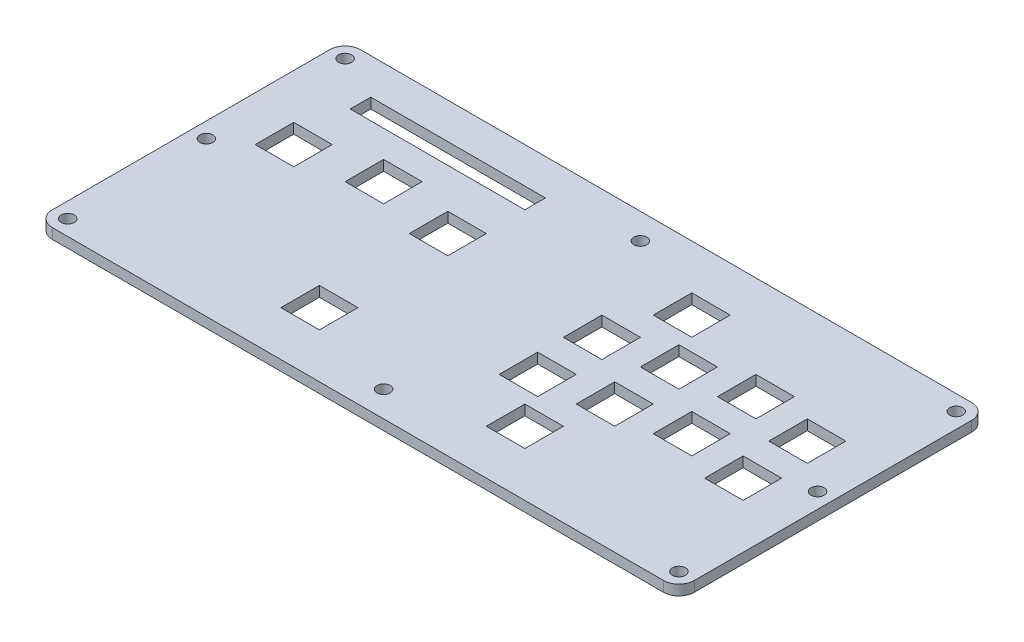
SolidWorks part; units mm, degrees
ref_plane "前视基准面" through (0, 0, 0) normal (0, 0, 1) x (1, 0, 0)
ref_plane "上视基准面" through (0, 0, 0) normal (0, 1, 0) x (1, 0, 0)
ref_plane "右视基准面" through (0, 0, 0) normal (1, 0, 0) x (0, 0, -1)
sketch "草图1" plane through (0, 0, 0) normal (0, 1, 0) x (1, 0, 0)
  line L0 (26.7276, 134.0406) -> (264.7276, 134.0406)
  line L1 (270.7276, 128.0406) -> (270.7276, 20.0406)
  line L2 (264.7276, 14.0406) -> (26.7276, 14.0406)
  line L3 (20.7276, 20.0406) -> (20.7276, 128.0406)
  line L4 (38.2276, 96.5406) -> (53.2276, 96.5406)
  line L5 (53.2276, 96.5406) -> (53.2276, 81.5406)
  line L6 (53.2276, 81.5406) -> (38.2276, 81.5406)
  line L7 (38.2276, 81.5406) -> (38.2276, 96.5406)
  line L8 (68.2276, 101.5406) -> (83.2276, 101.5406)
  line L9 (83.2276, 101.5406) -> (83.2276, 86.5406)
  line L10 (83.2276, 86.5406) -> (68.2276, 86.5406)
  line L11 (68.2276, 86.5406) -> (68.2276, 101.5406)
  line L12 (163.2276, 91.5406) -> (178.2276, 91.5406)
  line L13 (178.2276, 91.5406) -> (178.2276, 76.5406)
  line L14 (178.2276, 76.5406) -> (163.2276, 76.5406)
  line L15 (163.2276, 76.5406) -> (163.2276, 91.5406)
  line L16 (98.2276, 46.5406) -> (113.2276, 46.5406)
  line L17 (113.2276, 46.5406) -> (113.2276, 31.5406)
  line L18 (113.2276, 31.5406) -> (98.2276, 31.5406)
  line L19 (98.2276, 31.5406) -> (98.2276, 46.5406)
  line L20 (98.2276, 96.5406) -> (113.2276, 96.5406)
  line L21 (113.2276, 96.5406) -> (113.2276, 81.5406)
  line L22 (113.2276, 81.5406) -> (98.2276, 81.5406)
  line L23 (98.2276, 81.5406) -> (98.2276, 96.5406)
  line L24 (173.2276, 116.5406) -> (188.2276, 116.5406)
  line L25 (188.2276, 116.5406) -> (188.2276, 101.5406)
  line L26 (188.2276, 101.5406) -> (173.2276, 101.5406)
  line L27 (173.2276, 101.5406) -> (173.2276, 116.5406)
  line L28 (188.2276, 96.5406) -> (203.2276, 96.5406)
  line L29 (203.2276, 96.5406) -> (203.2276, 81.5406)
  line L30 (203.2276, 81.5406) -> (188.2276, 81.5406)
  line L31 (188.2276, 81.5406) -> (188.2276, 96.5406)
  line L32 (213.2276, 101.5406) -> (228.2276, 101.5406)
  line L33 (228.2276, 101.5406) -> (228.2276, 86.5406)
  line L34 (228.2276, 86.5406) -> (213.2276, 86.5406)
  line L35 (213.2276, 86.5406) -> (213.2276, 101.5406)
  line L36 (188.2276, 71.5406) -> (203.2276, 71.5406)
  line L37 (203.2276, 71.5406) -> (203.2276, 56.5406)
  line L38 (203.2276, 56.5406) -> (188.2276, 56.5406)
  line L39 (188.2276, 56.5406) -> (188.2276, 71.5406)
  line L40 (238.2276, 71.5406) -> (253.2276, 71.5406)
  line L41 (253.2276, 71.5406) -> (253.2276, 56.5406)
  line L42 (253.2276, 56.5406) -> (238.2276, 56.5406)
  line L43 (238.2276, 56.5406) -> (238.2276, 71.5406)
  line L44 (213.2276, 76.5406) -> (228.2276, 76.5406)
  line L45 (228.2276, 76.5406) -> (228.2276, 61.5406)
  line L46 (228.2276, 61.5406) -> (213.2276, 61.5406)
  line L47 (213.2276, 61.5406) -> (213.2276, 76.5406)
  line L48 (163.2276, 66.5406) -> (178.2276, 66.5406)
  line L49 (178.2276, 66.5406) -> (178.2276, 51.5406)
  line L50 (178.2276, 51.5406) -> (163.2276, 51.5406)
  line L51 (163.2276, 51.5406) -> (163.2276, 66.5406)
  line L52 (178.2276, 46.5406) -> (193.2276, 46.5406)
  line L53 (193.2276, 46.5406) -> (193.2276, 31.5406)
  line L54 (193.2276, 31.5406) -> (178.2276, 31.5406)
  line L55 (178.2276, 31.5406) -> (178.2276, 46.5406)
  line L56 (238.2276, 96.5406) -> (253.2276, 96.5406)
  line L57 (253.2276, 96.5406) -> (253.2276, 81.5406)
  line L58 (253.2276, 81.5406) -> (238.2276, 81.5406)
  line L59 (238.2276, 81.5406) -> (238.2276, 96.5406)
  line L60 (44.7276, 116.0406) -> (44.7276, 112.0406)
  line L61 (44.7276, 112.0406) -> (112.7276, 112.0406)
  line L62 (112.7276, 112.0406) -> (112.7276, 120.0406)
  line L63 (112.7276, 120.0406) -> (44.7276, 120.0406)
  line L64 (44.7276, 120.0406) -> (44.7276, 116.0406)
  line L65 (44.7276, 120.0406) -> (112.7276, 120.0406)
  line L66 (112.7276, 120.0406) -> (112.7276, 112.0406)
  line L67 (112.7276, 112.0406) -> (44.7276, 112.0406)
  line L68 (44.7276, 112.0406) -> (44.7276, 120.0406)
  arc A0 (26.7276, 134.0406) -> (20.7276, 128.0406) centre (26.7276, 128.0406) ccw
  arc A1 (270.7276, 128.0406) -> (264.7276, 134.0406) centre (264.7276, 128.0406) ccw
  arc A2 (264.7276, 14.0406) -> (270.7276, 20.0406) centre (264.7276, 20.0406) ccw
  arc A3 (20.7276, 20.0406) -> (26.7276, 14.0406) centre (26.7276, 20.0406) ccw
  circle A4 centre (26.7276, 128.0406) radius 2.55
  circle A5 centre (264.7276, 128.0406) radius 2.55
  circle A6 centre (145.7276, 124.0406) radius 2.55
  circle A7 centre (26.7276, 20.0406) radius 2.55
  circle A8 centre (264.7276, 20.0406) radius 2.55
  circle A9 centre (145.7276, 24.0406) radius 2.55
  circle A10 centre (264.7276, 74.0406) radius 2.55
  circle A11 centre (26.7276, 74.0406) radius 2.55
extrude "凸台-拉伸1" add sketch "草图1" along normal blind 4 contours L3 A3 L2 A2 L1 A1 L0 A0 A11 A10 A9 A8 A7 A6 A5 A4 L58 L59 L56 L57 L54 L55 L52 L53 L50 L51 L48 L49 L46 L47 L44 L45 L42 L43 L40 L41 L38 region at (144.323, 0, -72.864)
